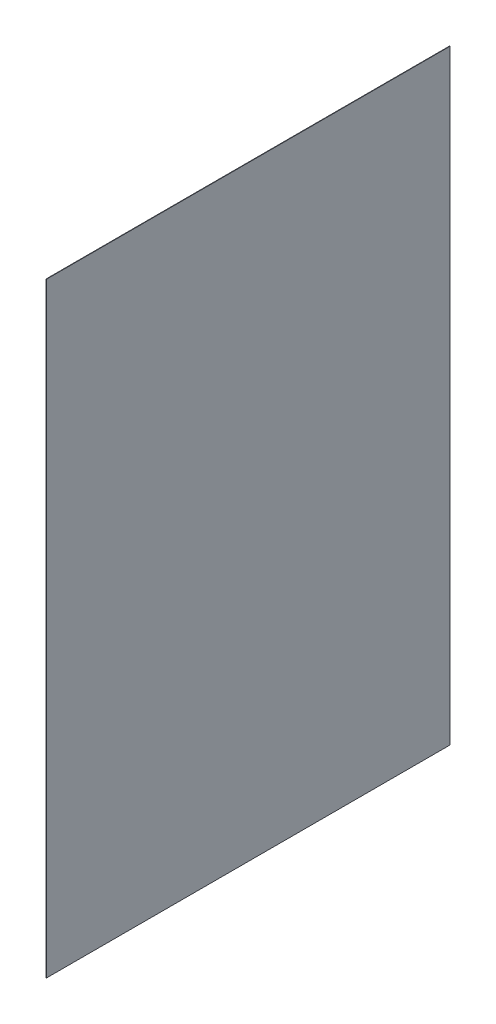
SolidWorks part; units mm, degrees
ref_plane "Front Plane" through (0, 0, 0) normal (0, 0, 1) x (1, 0, 0)
ref_plane "Top Plane" through (0, 0, 0) normal (0, 1, 0) x (1, 0, 0)
ref_plane "Right Plane" through (0, 0, 0) normal (1, 0, 0) x (0, 0, -1)
sketch "Sketch1" plane through (0, 0, 0) normal (1, 0, 0) x (0, 0, -1)
  line L1 (0, 0) -> (659, 0)
  line L2 (0, 0) -> (0, 988.4)
  line L3 (0, 988.4) -> (659, 988.4)
  line L4 (659, 0) -> (659, 988.4)
  dimension "D1" = 988.4
  dimension "D2" = 659
base flange "Base-Flange1" sketch "Sketch1" thickness 0.7 reverse thickness direction no parameters "D1"=0.7
sketch "Bend-Lines1" [suppressed] plane through (0, 0, 0) normal (0, 1, 0) x (1, 0, 0)
sketch "Bounding-Box1" [suppressed] plane through (0, 0, 0) normal (0, 1, 0) x (1, 0, 0)
sheet metal parameters "Sheet-Metal1" thickness 0.7 parameters "D1"=0.7
flat pattern "Flat-Pattern1" [suppressed]
sketch "Bend-Lines2" plane through (0, 0, 0) normal (0, 1, 0) x (1, 0, 0)
sketch3d "Bounding-Box2" [suppressed]
  line L0 (0, 808.4, 0) -> (0, 0, 0) construction
  line L1 (-801.7, 808.4, 0) -> (-801.7, 0, 0) construction
  line L2 (0, 808.4, 0) -> (-801.7, 808.4, 0) construction
  line L3 (0, 0, 0) -> (-801.7, 0, 0) construction
